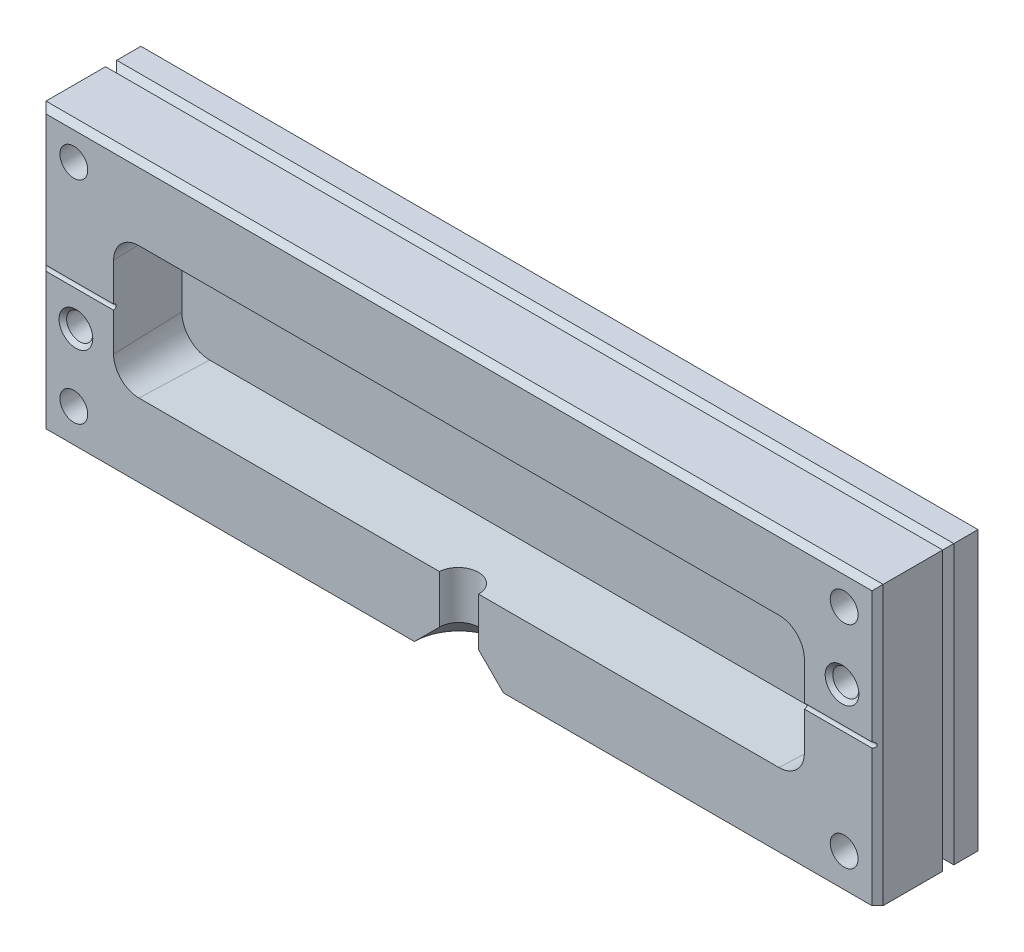
SolidWorks part; units mm, degrees
ref_plane "Front Plane" through (0, 0, 0) normal (0, 0, 1) x (1, 0, 0)
ref_plane "Top Plane" through (0, 0, 0) normal (0, 1, 0) x (1, 0, 0)
ref_plane "Right Plane" through (0, 0, 0) normal (1, 0, 0) x (0, 0, -1)
sketch "MoldSketch" plane through (0, 0, 0) normal (0, 0, 1) x (1, 0, 0)
  line L1 (-75.2, 25) -> (75.2, 25)
  line L2 (-75.2, 25) -> (-75.2, -25)
  line L3 (-75.2, -25) -> (75.2, -25)
  line L4 (75.2, 25) -> (75.2, -25)
  line L5 (-75.2, 25) -> (75.2, -25) construction
  line L6 (-75.2, -25) -> (75.2, 25) construction
  line L15 (-57.5, 12.3) -> (57.5, 12.3)
  line L16 (-62.5, 7.3) -> (-62.5, -7.3)
  line L17 (-57.5, -12.3) -> (57.5, -12.3)
  line L18 (62.5, 7.3) -> (62.5, -7.3)
  line L19 (-62.5, 12.3) -> (62.5, -12.3) construction
  line L20 (-62.5, -12.3) -> (62.5, 12.3) construction
  line L22 (0, 0) -> (0, 61.0569) construction
  line L25 (75.2, -58.9) -> (75.2, 7.3) construction
  line L26 (75.2, 7.3) -> (62.5, 7.3) construction
  line L27 (62.5, -7.3) -> (62.5, 7.3) construction
  arc A0 (57.5, 12.3) -> (62.5, 7.3) centre (57.5, 7.3) cw
  arc A1 (57.5, -12.3) -> (62.5, -7.3) centre (57.5, -7.3) ccw
  arc A2 (-62.5, -7.3) -> (-57.5, -12.3) centre (-57.5, -7.3) ccw
  arc A3 (-57.5, 12.3) -> (-62.5, 7.3) centre (-57.5, 7.3) ccw
  point P0 (0, 0)
  point P6 (0, 0)
  dimension "D5" = 5
  dimension "D1" = 150.4
  dimension "D2" = 50
  dimension "D3" = 12.7
  dimension "D4" = 12.7
  dimension "D12" = 125
extrude "MoldExtrusion12.7mm" add sketch "MoldSketch" along normal blind 12.7
sketch "CoverSketch" plane through (0, 0, 0) normal (0, 0, -1) x (-1, 0, 0)
  line L1 (-75.2, 25) -> (75.2, 25)
  line L2 (-75.2, 25) -> (-75.2, -25)
  line L3 (-75.2, -25) -> (75.2, -25)
  line L4 (75.2, 25) -> (75.2, -25)
extrude "CoverThickness" add sketch "CoverSketch" along normal blind 6.35 separate body
draft "Mold2DegDraft" type of draft neutral plane draft angle 2 faces to draft 8 face at (60.5178, -10.3178, 6.35) face at (62.5, 0, 6.35) face at (60.5178, 10.3178, 6.35) face at (0, 12.3, 6.35) face at (-60.5178, 10.3178, 6.35) face at (-62.5, 0, 6.35) face at (-60.5178, -10.3178, 6.35) face at (0, -12.3, 6.35) neutral plane through (0, 0, 0) neutral plane normal (0, 0, -1) parameters "D1"=2
sketch "DowelHolesLocations" plane through (0, 0, 12.7) normal (0, 0, 1) x (1, 0, 0)
  line L0 (75.2, 25) -> (-75.2, 25) construction
  line L1 (-75.2, 25) -> (-75.2, -25) construction
  line L2 (-75.2, -25) -> (75.2, -25) construction
  line L3 (75.2, -25) -> (75.2, 25) construction
  point P0 (-68.825, -6.75)
  point P5 (68.825, 6.75)
  dimension "D1" = 31.75
  dimension "D2" = 6.375
  dimension "D3" = 31.75
  dimension "D4" = 6.375
sketch "VentingHoleLocation" plane through (75.2, 0, 0) normal (1, 0, 0) x (0, 0, -1)
  line L0 (-12.7, -25) -> (-12.7, 25) construction
  point P0 (-12.7, 0)
hole_wizard "VentingHole" positions "3DSketch1" profile "Sketch14" hole size "M1.2x0.25" standard "ANSI Metric" end condition through all
sketch3d "3DSketch1"
  point P0 (75.2, 0, 12.7)
sketch "Sketch14" plane through (75.2, 0, 12.7) normal (0, 1, 0) x (0, 0, -1)
  line L0 (0, 0) -> (0, 150.4)
  line L1 (0, 150.4) -> (0.475, 150.4)
  line L2 (0.475, 150.4) -> (0.475, 0)
  line L5 (0.475, 0) -> (0, 0)
  line L11 (0, -6.35) -> (0, 107.95) construction
  dimension "Thru Hole Dia." = 0.95
  dimension "Thru Hole Depth" = 150.4
hole_wizard "Ø6.0mm Dowel Holes" positions "Sketch6" profile "Sketch7" hole size "Ø6.0" standard "ANSI Metric"
sketch "Sketch6" plane through (0, 0, 12.7) normal (0, 0, 1) x (1, 0, 0)
  point P0 (-68.825, -6.75)
  point P3 (68.825, 6.75)
sketch "Sketch7" plane through (-68.825, -6.75, 12.7) normal (1, 0, 0) x (0, -1, 0)
  line L0 (0, 0) -> (0, 9.412)
  line L1 (0, 9.412) -> (2.35, 8)
  line L2 (2.35, 8) -> (2.35, 0.68)
  line L3 (2.35, 0.68) -> (3.03, 0)
  line L5 (3.03, 0) -> (0, 0)
  line L6 (-2.35, 0.68) -> (-3.03, 0) construction
  line L10 (0, 9.412) -> (-2.35, 8) construction
  line L11 (0, -6.35) -> (0, 107.95) construction
  dimension "Hole Dia." = 4.7
  dimension "Hole Depth" = 8
  dimension "Near C'Sink Dia." = 6.06
  dimension "Near C'Sink Angle" = 90
  dimension "Drill Angle" = 118
hole_wizard "CSK for M6 Flat Head Machine Screw1" positions "InjecitonHoleLocation" profile "InjectionHole" countersink size "M6" standard "ANSI Metric"
sketch "InjecitonHoleLocation" plane through (0, -25, 0) normal (0, -1, 0) x (-1, 0, 0)
  line L1 (75.2, -12.7) -> (-75.2, -12.7) construction
  point P0 (0, -12.7)
sketch "InjectionHole" plane through (0, -25, 12.7) normal (1, 0, 0) x (0, 0, -1)
  line L0 (0, 0) -> (0, 13.1435)
  line L1 (0, 13.1435) -> (3.5, 13.1435)
  line L2 (3.5, 13.1435) -> (3.5, 4.5)
  line L3 (3.5, 4.5) -> (8, 0)
  line L5 (8, 0) -> (0, 0)
  line L6 (-3.5, 4.5) -> (-8, 0) construction
  line L10 (0, 13.1435) -> (-3.5, 13.1435) construction
  line L11 (0, -6.35) -> (0, 107.95) construction
  dimension "Hole Dia." = 7
  dimension "Hole Depth" = 13.1435
  dimension "Near C'Sink Dia." = 16
  dimension "Near C'Sink Angle" = 90
  dimension "Drill Angle" = 180
sketch "ThreadHolesLocations" plane through (0, 0, 0) normal (0, 0, -1) x (-1, 0, 0)
  line L0 (-75.2, -25) -> (-75.2, 25) construction
  line L1 (-75.2, 25) -> (75.2, 25) construction
  line L2 (0, 0) -> (0, -44.31) construction
  line L3 (0, 0) -> (82.7787, 0) construction
  point P0 (-69.2, 19)
  point P5 (-69.2, 19)
  point P14 (69.2, 19)
  point P16 (69.2, -19)
  point P17 (-69.2, -19)
  dimension "D1" = 6
  dimension "D2" = 6
chamfer "Chamfer1" distance 1 angle 45 9 edges at (0, 25, 12.7) (-75.2, -12.7375, 12.7) (-75.2, 12.7375, 12.7) (75.2, 12.7375, 12.7) (75.2, -12.7375, 12.7) (75.2, 0, 0) (0, 25, 0) (-75.2, 0, 0) (0, -25, 0)
sketch "CoverHolesLocations" plane through (0, 0, -6.35) normal (0, 0, -1) x (-1, 0, 0)
  line L0 (-37.9403, 19.2073) -> (-37.9403, -25.1027) construction
  line L1 (-37.9403, 19.2073) -> (44.8384, 19.2073) construction
  point P0 (-94.6403, 38.2073)
  point P1 (-94.6403, 38.2073)
  point P6 (18.7597, 38.2073)
  point P7 (18.7597, 0.2073)
  point P8 (-94.6403, 0.2073)
hole_wizard "Tap Drill for M6x1.0 Tap1" positions "Sketch8" profile "Sketch9" hole size "M6x1.0" standard "ANSI Metric" end condition through all
sketch "Sketch8" plane through (-40.3988, -67.586, 0) normal (0, 0, -1) x (-1, 0, 0)
  point P0 (-109.5988, 86.586)
  point P3 (28.8012, 86.586)
  point P6 (28.8012, 48.586)
  point P9 (-109.5988, 48.586)
sketch "Sketch9" plane through (69.2, 19, 0) normal (1, 0, 0) x (0, 1, 0)
  line L0 (0, 0) -> (0, 12.7)
  line L1 (0, 12.7) -> (2.5, 12.7)
  line L2 (2.5, 12.7) -> (2.5, 0)
  line L5 (2.5, 0) -> (0, 0)
  line L11 (0, -6.35) -> (0, 107.95) construction
  dimension "Thru Hole Dia." = 5
  dimension "Thru Hole Depth" = 12.7
chamfer "CoverChamfer" distance 1 angle 45 8 edges at (75.2, 0, 0) (0, -25, 0) (-75.2, 0, 0) (0, 25, 0) (-75.2, 0, -6.35) (0, -25, -6.35) (75.2, 0, -6.35) (0, 25, -6.35)
hole_wizard "Tap Drill for M6x1.0 Tap2" positions "Sketch10" profile "Sketch11" hole size "M6x1.0" standard "ANSI Metric" end condition through all
sketch "Sketch10" plane through (-40.3988, -67.586, 0) normal (0, 0, 1) x (1, 0, 0)
  point P0 (-28.8012, 86.586)
  point P3 (109.5988, 86.586)
  point P6 (109.5988, 48.586)
  point P9 (-28.8012, 48.586)
sketch "Sketch11" plane through (-69.2, 19, 0) normal (1, 0, 0) x (0, -1, 0)
  line L0 (0, 0) -> (0, 6.35)
  line L1 (0, 6.35) -> (2.5, 6.35)
  line L2 (2.5, 6.35) -> (2.5, 0)
  line L3 (2.5, 0) -> (0, 0)
  line L4 (0, -6.35) -> (0, 107.95) construction
  dimension "Thru Hole Dia." = 5
  dimension "Thru Hole Depth" = 6.35
